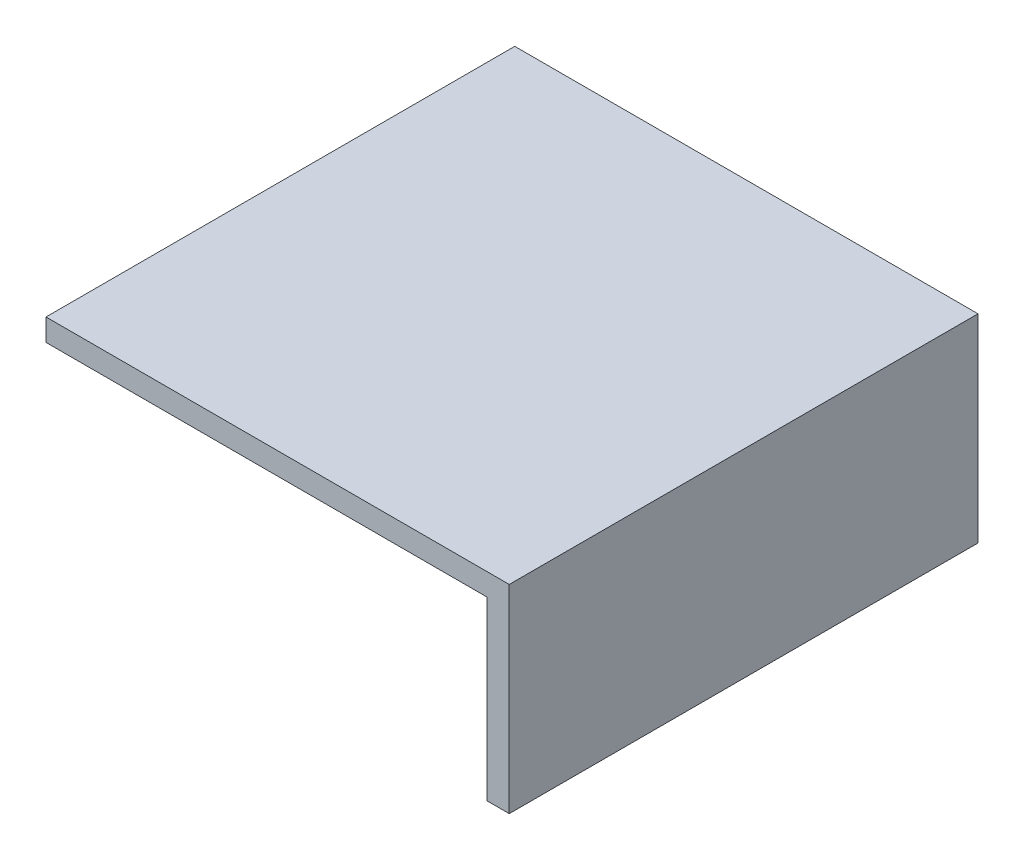
SolidWorks part; units mm, degrees
ref_plane "Front Plane" through (0, 0, 0) normal (0, 0, 1) x (1, 0, 0)
ref_plane "Top Plane" through (0, 0, 0) normal (0, 1, 0) x (1, 0, 0)
ref_plane "Right Plane" through (0, 0, 0) normal (1, 0, 0) x (0, 0, -1)
sketch "Sketch1" plane through (0, 0, 0) normal (0, 0, 1) x (1, 0, 0)
  line L0 (21, 1) -> (21, -17)
  line L1 (-21, -1) -> (19, -1)
  line L2 (-21, -1) -> (-21, 1)
  line L3 (-21, 1) -> (21, 1)
  line L4 (-21, 1) -> (0, 0) construction
  line L5 (0, 0) -> (-21, -1) construction
  line L6 (0, 0) -> (21, 1) construction
  line L9 (21, -17) -> (19, -17)
  line L10 (19, -1) -> (19, -17)
  point P0 (0, 0)
  dimension "D1" = 40
  dimension "D2" = 16
  dimension "D3" = 2
  dimension "D4" = 2
extrude "Boss-Extrude1" add sketch "Sketch1" against normal blind 21.25 and the other way blind 21.25
